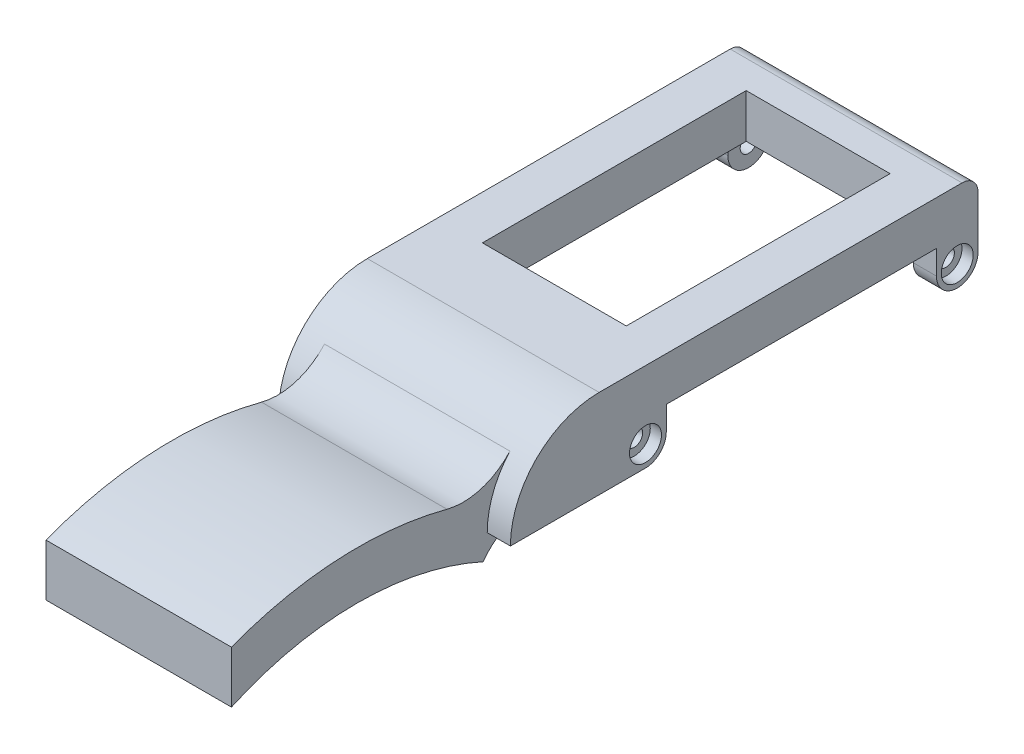
SolidWorks part; units mm, degrees
ref_plane "Front Plane" through (0, 0, 0) normal (0, 0, 1) x (1, 0, 0)
ref_plane "Top Plane" through (0, 0, 0) normal (0, 1, 0) x (1, 0, 0)
ref_plane "Right Plane" through (0, 0, 0) normal (1, 0, 0) x (0, 0, -1)
sketch "Sketch1" plane through (0, 0, 0) normal (0, 1, 0) x (1, 0, 0)
  line L1 (-14.5, 22) -> (14.5, 22)
  line L2 (-14.5, 22) -> (-14.5, -22)
  line L3 (-14.5, -22) -> (14.5, -22)
  line L4 (14.5, 22) -> (14.5, -22)
  line L5 (-14.5, 22) -> (14.5, -22) construction
  line L6 (-14.5, -22) -> (14.5, 22) construction
  line L7 (-9, -16.5) -> (9, -16.5)
  line L8 (-9, -16.5) -> (-9, 16.5)
  line L9 (-9, 16.5) -> (9, 16.5)
  line L10 (9, -16.5) -> (9, 16.5)
  line L11 (-9, -16.5) -> (9, 16.5) construction
  line L12 (-9, 16.5) -> (9, -16.5) construction
  point P0 (0, 0)
  point P6 (0, 0)
  dimension "D1" = 29
  dimension "D2" = 44
  dimension "D3" = 33
  dimension "D4" = 18
extrude "Boss-Extrude1" add sketch "Sketch1" along normal blind 5.5
sketch "Sketch2" plane through (14.5, 0, 0) normal (1, 0, 0) x (0, 0, -1)
  line L0 (22, 0) -> (22, -3)
  line L1 (16.8, -3) -> (16.8, 0)
  line L2 (-22, 0) -> (22, 0) construction
  line L3 (16.8, 0) -> (22, 0)
  line L5 (19.4, -5.6) -> (-36.5, -5.6) construction
  line L6 (-22, 5.5) -> (22, 5.5) construction
  line L7 (-17, -3) -> (-17, 0)
  line L8 (-17, 0) -> (-22, 0)
  line L9 (-22, 0) -> (-22, 5.5)
  line L10 (-36.5, -5.6) -> (-36.5, -13.8799) construction
  line L11 (-25.4, 5.5) -> (-22, 5.5)
  line L12 (-19.6, -5.6) -> (-36.5, -5.6)
  circle A0 centre (19.4, -3) radius 2.6
  circle A1 centre (19.4, -3) radius 1.05
  circle A2 centre (19.4, -3) radius 2
  arc A3 (-25.4, 5.5) -> (-36.5, -5.6) centre (-25.4, -5.6) ccw
  circle A4 centre (-19.6, -3) radius 2.6
  circle A5 centre (-19.6, -3) radius 2
  circle A6 centre (-19.6, -3) radius 1.05
  line M10 (-22, 0) -> (22, 0)
  line M13 (-22, 5.5) -> (-22, 0)
  dimension "D1" = 5.2
  dimension "D2" = 4
  dimension "D3" = 2.1
  dimension "D4" = 8.5
  dimension "D5" = 39
  dimension "D6" = 19.5
extrude "Boss-Extrude2" add sketch "Sketch2" against normal blind 2.9 contours A4 L7 L11 A3 L12 M10 M13 | A4 A5 | A0 A2 | A0 L0 L1 M10 | A5 A6 | A2 A1 region at (14.5, -0.6817, 27.9821) region at (14.5, -1.5, -21.94) region at (14.5, -5.5265, -19.4) region at (14.5, -4.7865, 17.8135) region at (14.5, -3, -17.4566) region at (14.5, -3, 21.5434)
extrude "Cut-Extrude1" cut sketch "Sketch2<4>" against normal blind 1.4 contours A5 A6 | A2 A1 region at (14.5, -3, -17.4566) region at (14.5, -3, 21.5434)
sketch "Sketch2<4>" plane through (14.5, 0, 0) normal (1, 0, 0) x (0, 0, -1) same geometry as "Sketch2"
mirror "Mirror1" about plane through (0, 0, 0) normal (1, 0, 0) of "Cut-Extrude1", "Boss-Extrude2"
sketch "Sketch3" plane through (0, 0, 0) normal (1, 0, 0) x (0, 0, -1)
  line L0 (-22, 0) -> (-34.9838, 0)
  line L1 (-31.5, 0) -> (-31.5, -5.6)
  line L2 (-68.5, -8.5) -> (-68.5, -2)
  line L3 (-37, -2) -> (-37, -8.5) construction
  line L4 (-39.5285, -0.8) -> (-36.0612, -0.8) construction
  line L5 (-36.5, -5.6) -> (-19.6, -5.6)
  line L6 (-17, -3) -> (-17, 0)
  line L7 (-17, 0) -> (-22, 0)
  line L8 (-22, 0) -> (-22, 5.5)
  line L9 (-22, 5.5) -> (-25.4, 5.5)
  line L10 (-36.5, -5.6) -> (-19.6, -5.6)
  line L11 (-17, -3) -> (-17, 0)
  line L12 (-17, 0) -> (-22, 0)
  line L13 (-22, 0) -> (-22, 5.5)
  line L14 (-22, 5.5) -> (-25.4, 5.5)
  arc A0 (-31.5, -5.6) -> (-37, -8.5) centre (-31.5, -12.2655) ccw
  arc A1 (-37, -8.5) -> (-68.5, -8.5) centre (-52.75, -43.1689) ccw
  arc A2 (-19.6, -5.6) -> (-17, -3) centre (-19.6, -3) ccw
  arc A3 (-25.4, 5.5) -> (-36.5, -5.6) centre (-25.4, -5.6) ccw
  arc A4 (-19.6, -5.6) -> (-17, -3) centre (-19.6, -3) ccw
  arc A5 (-25.4, 5.5) -> (-36.5, -5.6) centre (-25.4, -5.6) ccw
  arc A6 (-68.5, -2) -> (-37, -2) centre (-52.75, -43.1689) cw
  arc A7 (-41.5363, -0.5403) -> (-33.6573, 1.818) centre (-39.5285, 7.0924) ccw
  dimension "D7" = 6
  dimension "D8" = 4.8
  dimension "D2" = 5
  dimension "D3" = 6.5
  dimension "D4" = 32
  dimension "D5" = 14
  dimension "D6" = 20
  dimension "D1" = 0
extrude "Boss-Extrude4" add sketch "Sketch3" against normal up to surface and the other way up to surface contours A7 A6 L2 A1 A0 L10 A5 | L0 A5 L10 L1 | L14 A5 L0 L13 region at (0, 2.4199, 27.3332) region at (0, -2.9545, 33.7768) region at (0, -3.1636, 51.7117) up to face at (-11.6, -0.2057, 23.0372) other way up to face at (11.6, -0.2057, 23.0372)
fillet "Fillet1" radius 2 1 edges at (0, 5.5, -22)
